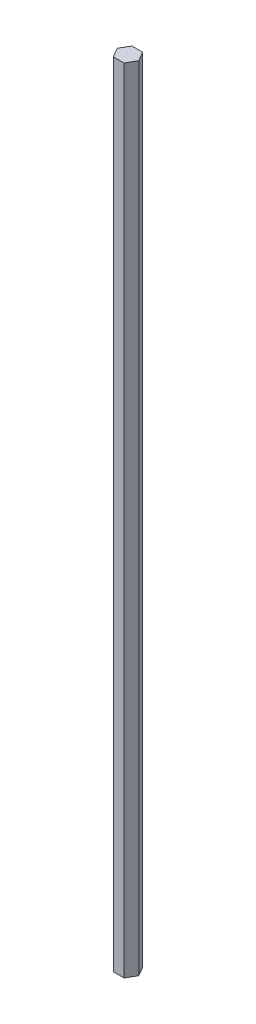
SolidWorks part; units mm, degrees
material "6061-T6 (SS)"
ref_plane "Front" through (0, 0, 0) normal (0, 0, 1) x (1, 0, 0)
ref_plane "Top" through (0, 0, 0) normal (0, 1, 0) x (1, 0, 0)
ref_plane "Right" through (0, 0, 0) normal (1, 0, 0) x (0, 0, -1)
sketch "Sketch1" plane through (0, 0, 0) normal (0, 1, 0) x (1, 0, 0)
  line L1 (7.3323, 0) -> (3.6662, 6.35)
  line L2 (3.6662, 6.35) -> (-3.6662, 6.35)
  line L3 (-3.6662, 6.35) -> (-7.3323, 0)
  line L4 (-7.3323, 0) -> (-3.6662, -6.35)
  line L5 (-3.6662, -6.35) -> (3.6662, -6.35)
  line L6 (3.6662, -6.35) -> (7.3323, 0)
  circle A0 centre (0, 0) radius 6.35 construction
  dimension "D1" = 12.7
extrude "Boss-Extrude1" add sketch "Sketch1" along normal blind 539.75
ref_axis "Axis1" through (0, 50, 0) along (0, -1, 0)
